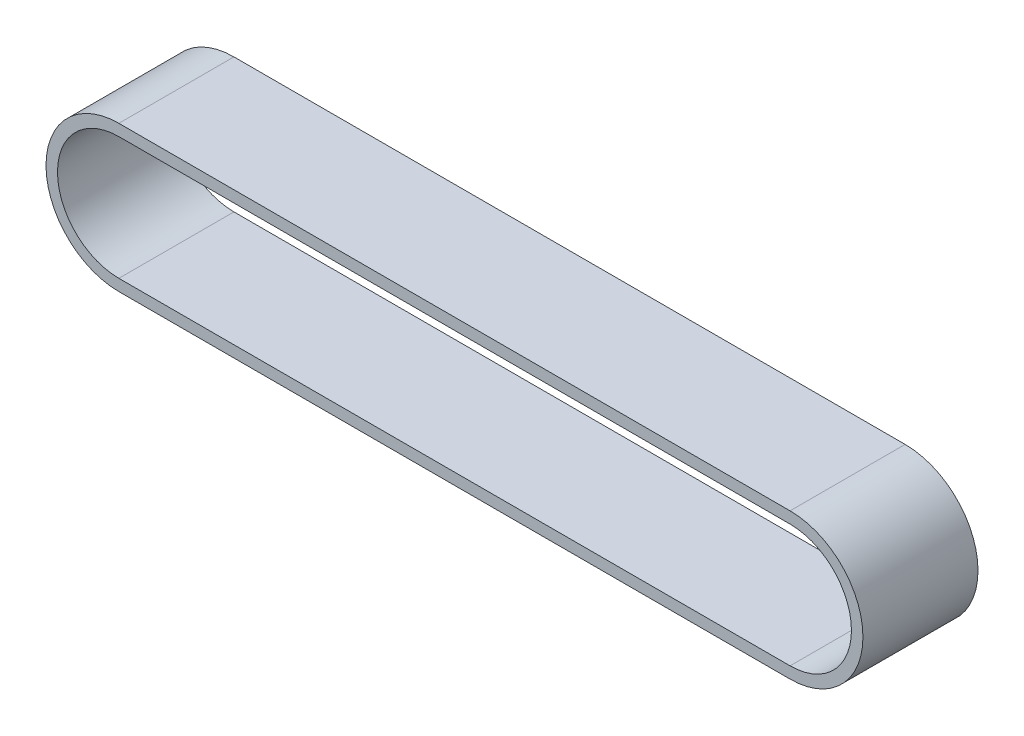
SolidWorks part; units mm, degrees
material "Silicon Rubber"
ref_plane "Front Plane" through (0, 0, 0) normal (0, 0, 1) x (1, 0, 0)
ref_plane "Top Plane" through (0, 0, 0) normal (0, 1, 0) x (1, 0, 0)
ref_plane "Right Plane" through (0, 0, 0) normal (1, 0, 0) x (0, 0, -1)
sketch "Sketch1" plane through (0, 0, 0) normal (0, 0, 1) x (1, 0, 0)
  line L0 (87.5, 0) -> (-87.5, 0) construction
  line L1 (87.5, -16) -> (-87.5, -16)
  line L2 (87.5, 16) -> (-87.5, 16)
  line L3 (87.5, -19) -> (-87.5, -19)
  line L4 (87.5, 19) -> (-87.5, 19)
  arc A0 (87.5, -16) -> (87.5, 16) centre (87.5, 0) ccw
  arc A1 (-87.5, 16) -> (-87.5, -16) centre (-87.5, 0) ccw
  arc A2 (-87.5, 19) -> (-87.5, -19) centre (-87.5, 0) ccw
  arc A3 (87.5, -19) -> (87.5, 19) centre (87.5, 0) ccw
  point P2 (0, 0)
  dimension "D1" = 16
  dimension "D2" = 175
  dimension "D3" = 3
extrude "Boss-Extrude1" add sketch "Sketch1" along normal blind 30
